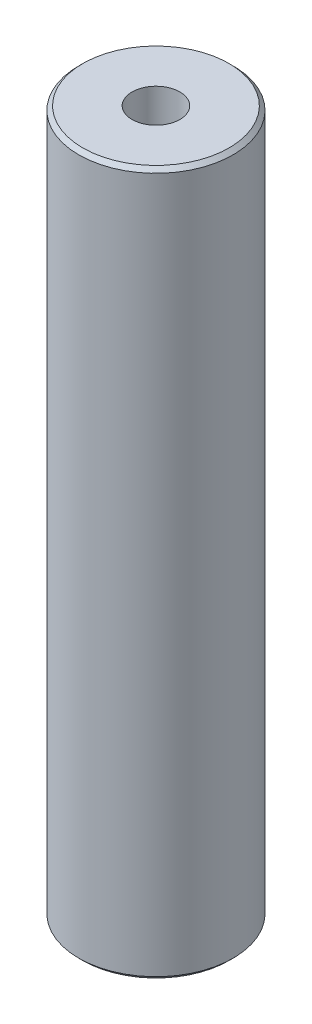
SolidWorks part; units mm, degrees
ref_plane "Front Plane" through (0, 0, 0) normal (0, 0, 1) x (1, 0, 0)
ref_plane "Top Plane" through (0, 0, 0) normal (0, 1, 0) x (1, 0, 0)
ref_plane "Right Plane" through (0, 0, 0) normal (1, 0, 0) x (0, 0, -1)
sketch "Sketch1" plane through (0, 0, 0) normal (0, 1, 0) x (1, 0, 0)
  circle A0 centre (0, 0) radius 60
  dimension "SHAFT_OD" = 120
extrude "Boss-Extrude1" add sketch "Sketch1" along normal blind 547.3338
sketch "Sketch2" plane through (0, 0, 0) normal (0, 1, 0) x (1, 0, 0)
  circle A0 centre (0, 0) radius 18.5952
  dimension "BORE_D" = 37.1903
extrude "Cut-Extrude1" cut sketch "Sketch2" along normal through all
chamfer "Chamfer1" distance 3.1138 angle 45 2 edges at (0, 547.3338, 60) (0, 0, 60)
